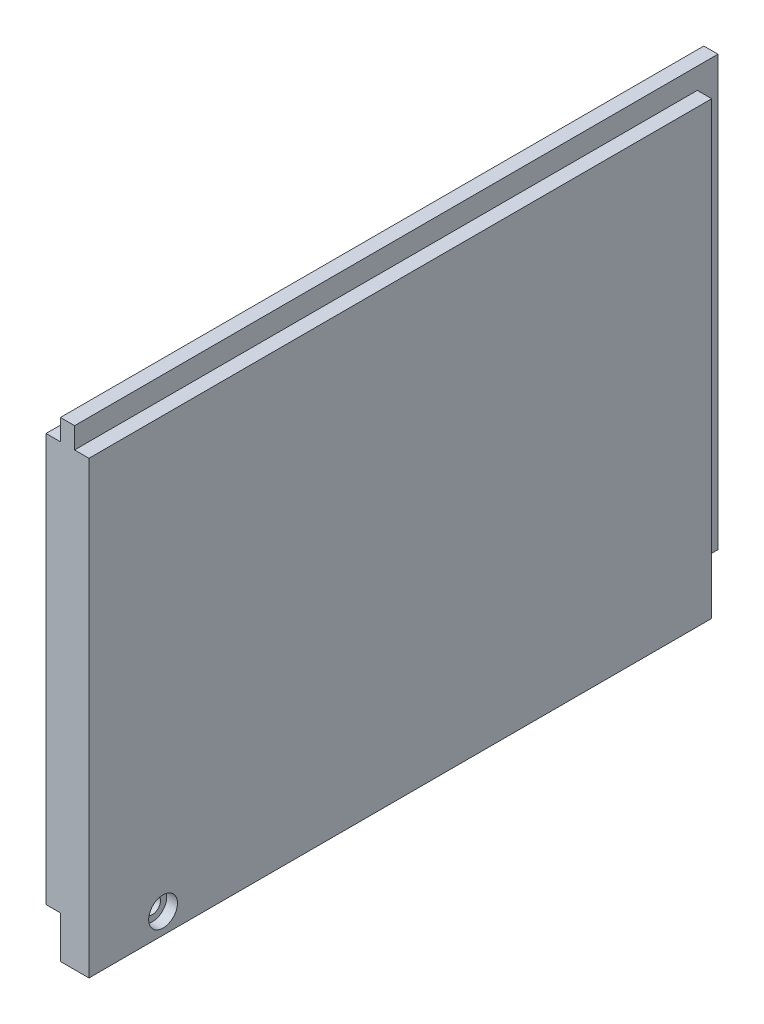
SolidWorks part; units mm, degrees
ref_plane "Front Plane" through (0, 0, 0) normal (1, 0, 0) x (0, 1, 0)
ref_plane "Top Plane" through (0, 0, 0) normal (0, 0, 1) x (0, 1, 0)
ref_plane "Right Plane" through (0, 0, 0) normal (0, 1, 0) x (-1, 0, 0)
sketch "Sketch2" plane through (0, 0, 0) normal (1, 0, 0) x (0, 1, 0)
  line L1 (0, 0) -> (95, 0)
  line L2 (0, 0) -> (0, 145)
  line L3 (0, 145) -> (95, 145)
  line L4 (95, 0) -> (95, 145)
  dimension "D1" = 95
  dimension "D2" = 145
extrude "Boss-Extrude1" add sketch "Sketch2" along normal blind 10
sketch "Sketch3" plane through (0, 95, 0) normal (0, 1, 0) x (-1, 0, 0)
  line L1 (-10, 0) -> (-6.65, 0) construction
  line L2 (-10, 0) -> (-10, -4.8) construction
  line L3 (-10, -4.8) -> (-6.65, -4.8) construction
  line L4 (-6.65, 0) -> (-6.65, -4.8) construction
  line L5 (0, 0) -> (-3.35, 0) construction
  line L6 (0, 0) -> (0, -4.8) construction
  line L7 (0, -4.8) -> (-3.35, -4.8) construction
  line L8 (-3.35, 0) -> (-3.35, -4.8) construction
  line L9 (-6.65, -4.8) -> (-3.35, -4.8)
  line L10 (-6.65, -4.8) -> (-6.65, 0)
  line L11 (-6.65, 0) -> (-3.35, 0)
  line L12 (-3.35, -4.8) -> (-3.35, 0)
  dimension "D1" = 3.35
  dimension "D2" = 3.35
  dimension "D3" = 4.8
extrude "Boss-Extrude3" add sketch "Sketch3" against normal up to surface (95 mm away) up to face at (5, 0, 72.5)
sketch "Sketch4" plane through (0, 95, 0) normal (0, 1, 0) x (-1, 0, 0)
  line L1 (-10, 145) -> (-6.65, 145) construction
  line L2 (-10, 145) -> (-10, -4.8) construction
  line L3 (-10, -4.8) -> (-6.65, -4.8) construction
  line L4 (-6.65, 145) -> (-6.65, -4.8) construction
  line L5 (-3.35, -4.8) -> (0, -4.8) construction
  line L6 (-3.35, -4.8) -> (-3.35, 145) construction
  line L7 (-3.35, 145) -> (0, 145) construction
  line L8 (0, -4.8) -> (0, 145) construction
  line L9 (-3.35, 145) -> (-6.65, 145)
  line L10 (-3.35, 145) -> (-3.35, -4.8)
  line L11 (-3.35, -4.8) -> (-6.65, -4.8)
  line L12 (-6.65, 145) -> (-6.65, -4.8)
  dimension "D1" = 3.3
extrude "Boss-Extrude4" add sketch "Sketch4" along normal blind 4.9
sketch "Sketch5" plane through (0, 0, 0) normal (0, -1, 0) x (1, 0, 0)
  line L0 (3.35, 0) -> (0, 0) construction
  line L1 (0, 145) -> (3.35, 145)
  line L2 (0, 145) -> (0, 0)
  line L3 (0, 0) -> (3.35, 0)
  line L4 (3.35, 145) -> (3.35, 0)
  line L6 (3.35, 0) -> (10, 0)
  line L7 (3.35, 0) -> (3.35, 145)
  line L8 (3.35, 145) -> (10, 145)
  line L9 (10, 0) -> (10, 145)
  line M6 (6.65, 0) -> (10, 0)
  line M7 (10, 0) -> (10, 145)
  line M8 (10, 145) -> (0, 145)
  dimension "D1" = 3.35
  dimension "D2" = 6.65
extrude "Boss-Extrude5" add sketch "Sketch5" along normal blind 10 contours L4 L6 M6 M7 M8 region at (6.675, 0, 72.5)
sketch "Sketch6" plane through (10, 0, 0) normal (1, 0, 0) x (0, 1, 0)
  line L1 (-10, 145) -> (-5, 145) construction
  line L2 (-10, 145) -> (-10, 127.75) construction
  line L3 (-10, 127.75) -> (-5, 127.75) construction
  line L4 (-5, 145) -> (-5, 127.75) construction
  circle A0 centre (-5, 127.75) radius 1.9
  dimension "D3" = 3.8
  dimension "D1" = 17.25
  dimension "D2" = 5
extrude "Cut-Extrude1" cut sketch "Sketch6" against normal up to next
sketch "Sketch8" plane through (10, 0, 0) normal (1, 0, 0) x (0, 1, 0)
  circle A0 centre (-5, 127.75) radius 3.35
  dimension "D1" = 6.7
extrude "Cut-Extrude3" cut sketch "Sketch8" against normal blind 2.5
sketch "Sketch7" plane through (10, 0, 0) normal (1, 0, 0) x (0, 1, 0)
  line L0 (-10, 0) -> (-10, 145) construction
  line L1 (-10, 145) -> (-9.8, 145)
  line L2 (-10, 145) -> (-10, 0)
  line L3 (-10, 0) -> (-9.8, 0)
  line L4 (-9.8, 145) -> (-9.8, 0)
  line L5 (-10, 0) -> (95, 0) construction
  point P8 (-10, 141.9969)
  point P9 (-10, 145)
  point P10 (-10, 145)
extrude "Cut-Extrude2" cut sketch "Sketch7" against normal up to next
sketch "Sketch9" plane through (0, 0, 0) normal (-1, 0, 0) x (0, -1, 0)
  line L0 (-90, 5) -> (-90, 140)
  line L1 (-95, 0) -> (0, 0)
  line L2 (-95, 0) -> (-95, 145)
  line L3 (-95, 145) -> (0, 145)
  line L4 (0, 0) -> (0, 145)
  line L5 (-90, 140) -> (-5, 140)
  line L6 (-5, 5) -> (-5, 140)
  line L7 (-90, 5) -> (-5, 5)
  dimension "D1" = 5
extrude "Cut-Extrude4" cut sketch "Sketch9" against normal blind 5 contours L0 L7 L6 L5 region at (0, 47.5, 72.5)
chamfer "Chamfer1" distance 5 distance2 2.5 4 edges at (0, 47.5, 5) (0, 5, 72.5) (0, 90, 72.5) (0, 47.5, 140) first distance on face at (2.5, 47.5, 5) first distance on face at (2.5, 5, 72.5) first distance on face at (2.5, 90, 72.5) first distance on face at (2.5, 47.5, 140)
equation "\"whitekey_cutout_length\"= 101.5"
equation "\"whitekey_spacing\"=1.25"
equation "\"key_mount_recess_length\"=50"
equation "\"key_mount_recess_height\"=12.5"
equation "\"key_mount_recess_depth\"=1.5"
equation "\"wall_thickness\"=10"
equation "\"guide_brace_height\"=20"
equation "\"guide_brace_thickness\"=2"
equation "\"dowel_recess_depth\"=10"
equation "\"dowel_recess_offset\"=3.25"
equation "\"dowel_insert_tolerance\"=0.1"
equation "\"base_mount_height\"=40"
equation "\"base_rear_length\"=80"
equation "\"base_front_length\"=111.5"
equation "\"screw_hole_wall_offset\"=7.25"
equation "\"screw_hole_edge_inset\"=\"dowel_recess_depth\"/2"
equation "\"screw_hole_diameter\"=3.8"
equation "\"screw_head_hole_diameter\"=6.7"
equation "\"screw_nut_hole_side_len\"=3.5"
equation "\"screw_nut_recess_offset\"=0.35"
equation "\"screw_head_and_nut_recess_depth\"=2.5"
equation "\"screw_shaft_diameter\"=3.5"
equation "\"switch_board_width\"=30"
equation "\"switch_board_thickness\"=1.6"
equation "\"switch_board_wall_offset\"=11.5"
equation "\"heatset_insert_hole_diameter\"=4.8"
equation "\"heatset_insert_hole_depth\"=3.8"
equation "\"front_rear_panel_width\"=23.75"
equation "\"front_panel_height\"=24"
equation "\"front_rear_panel_recess_depth\"=5"
equation "\"rod_diameter\"=5"
equation "\"rod_head_diameter\"=8"
equation "\"rod_length_adj\"=0.5"
equation "\"rod_insert_length\"=2.8"
equation "\"switch_black_key_mount_height\"=8"
equation "\"switch_white_key_mount_height\"=3"
equation "\"side_panel_depth\"=35"
equation "\"interface_panel_height\"=135"
equation "\"interface_panel_roof_length\"=50"
equation "\"D1@Sketch2\"=\"front_rear_panel_width\"*4"
equation "\"D2@Sketch2\"=\"interface_panel_height\"+\"wall_thickness\""
equation "\"D1@Boss-Extrude1\"=\"wall_thickness\""
equation "\"D1@Sketch3\"=\"dowel_recess_offset\"+\"dowel_insert_tolerance\""
equation "\"D2@Sketch3\"=\"dowel_recess_offset\"+\"dowel_insert_tolerance\""
equation "\"D3@Sketch3\"=\"front_rear_panel_recess_depth\"-\"dowel_insert_tolerance\"*2"
equation "\"D1@Boss-Extrude4\"=\"front_rear_panel_recess_depth\"-\"dowel_insert_tolerance\""
equation "\"D1@Sketch5\"=\"dowel_recess_offset\"+\"dowel_insert_tolerance\""
equation "\"D1@Boss-Extrude5\"=\"dowel_recess_depth\""
equation "\"D1@Sketch6\"=\"wall_thickness\"+\"screw_hole_wall_offset\""
equation "\"D2@Sketch6\"=\"screw_hole_edge_inset\""
equation "\"D3@Sketch6\"=\"screw_hole_diameter\""
equation "\"D1@Sketch7\"=\"dowel_insert_tolerance\"*2"
equation "\"D1@Sketch8\"=\"screw_head_hole_diameter\""
equation "\"D1@Cut-Extrude3\"=\"screw_head_and_nut_recess_depth\""
equation "\"D1@Cut-Extrude4\"=\"wall_thickness\"/2"
